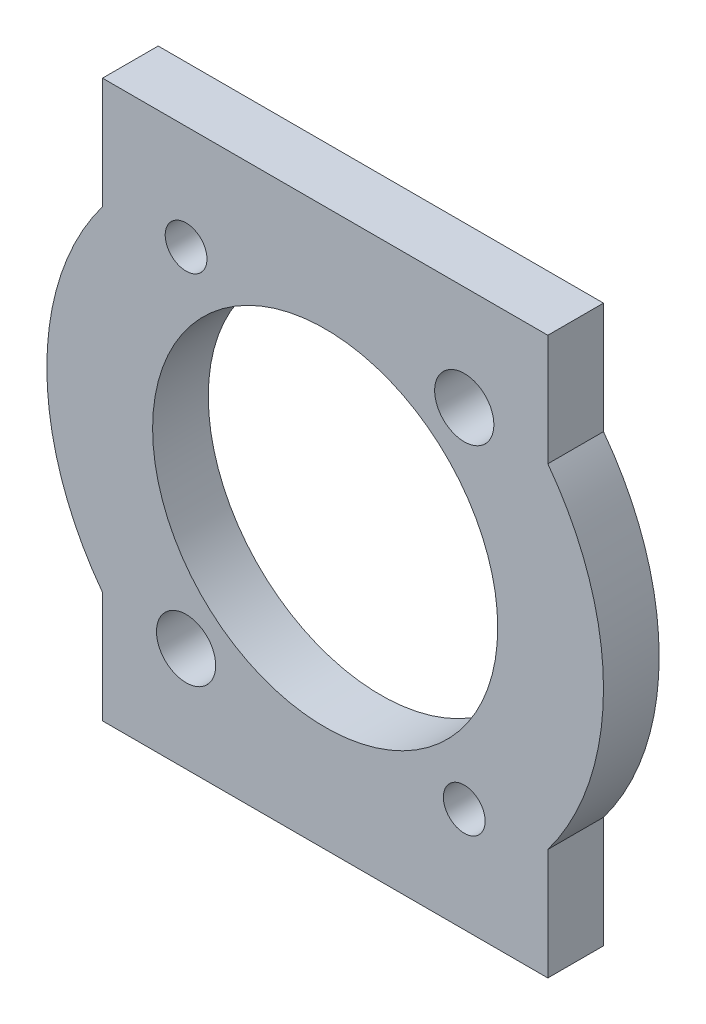
SolidWorks part; units mm, degrees
material "6061 Alloy"
ref_plane "Front" through (0, 0, 0) normal (0, 0, 1) x (1, 0, 0)
ref_plane "Top" through (0, 0, 0) normal (0, 1, 0) x (1, 0, 0)
ref_plane "Right" through (0, 0, 0) normal (1, 0, 0) x (0, 0, -1)
sketch "Sketch1" plane through (0, 0, 0) normal (0, 0, 1) x (1, 0, 0)
  line L0 (-50.8, 63.5) -> (0, 0) construction
  line L1 (0, 0) -> (-50.8, 0)
  line L2 (0, 0) -> (0, 12.7)
  line L3 (0, 63.5) -> (-50.8, 63.5)
  line L4 (-50.8, 0) -> (-50.8, 12.7)
  line L5 (0, 63.5) -> (-50.8, 0) construction
  line L6 (0, 50.8) -> (0, 63.5)
  line L7 (-50.8, 50.8) -> (-50.8, 63.5)
  circle A0 centre (-25.4, 31.75) radius 19.685
  arc A1 (-50.8, 50.8) -> (-50.8, 12.7) centre (-25.4, 31.75) ccw
  circle A2 centre (-25.4, 31.75) radius 25.4 construction
  arc A3 (0, 12.7) -> (0, 50.8) centre (-25.4, 31.75) ccw
  circle A4 centre (-41.2673, 51.5841) radius 2.3812
  circle A5 centre (-9.5327, 51.5841) radius 3.3782
  circle A6 centre (-9.5327, 11.9159) radius 2.3813
  circle A7 centre (-41.2673, 11.9159) radius 3.3782
  point P20 (-41.2673, 51.5841)
  point P21 (-9.5327, 51.5841)
  point P22 (-9.5327, 11.9159)
  point P23 (-41.2673, 11.9159)
  dimension "D2" = 39.37
  dimension "D4" = 50.8
  dimension "D5" = 4.7625
  dimension "D6" = 6.7564
  dimension "D1" = 50.8
  dimension "D3" = 31.75
extrude "Boss-Extrude1" add sketch "Sketch1" along normal blind 6.35
